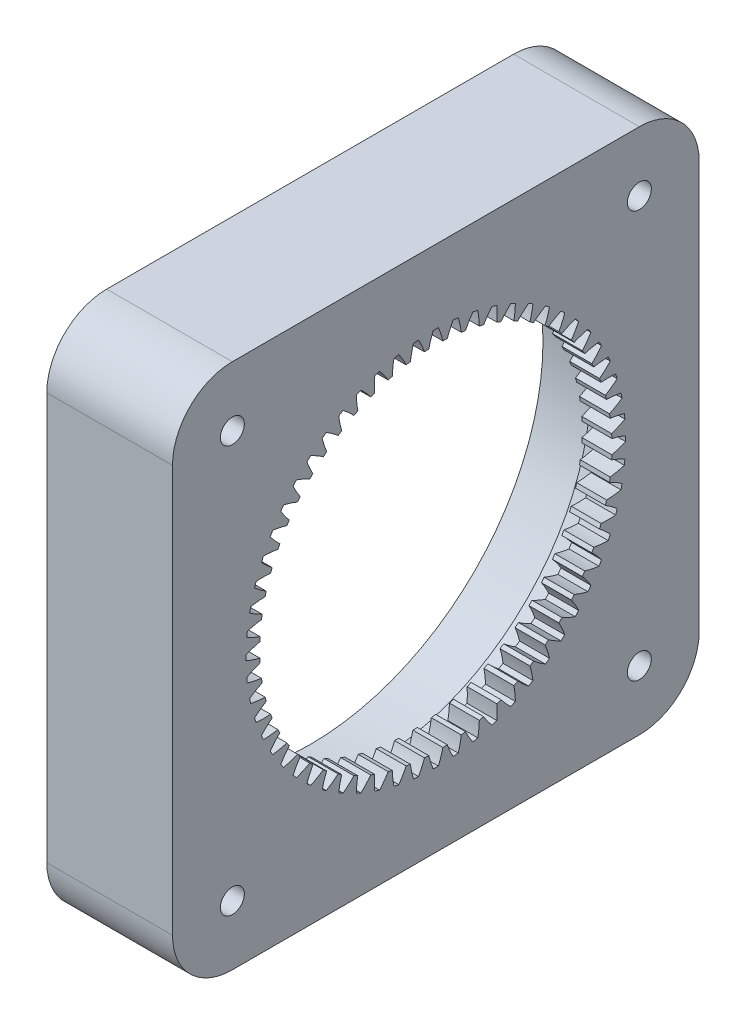
SolidWorks part; units mm, degrees
ref_plane "Plane1" through (0, 0, 0) normal (0, 0, 1) x (1, 0, 0)
ref_plane "Plane2" through (0, 0, 0) normal (0, 1, 0) x (1, 0, 0)
ref_plane "Plane3" through (0, 0, 0) normal (1, 0, 0) x (0, 0, -1)
other "Configuration Table"
sketch "HoldingSke" plane through (0, 0, 0) normal (0, 1, 0) x (1, 0, 0)
  line L0 (0, 0) -> (0.4926, -0.8532)
  line L1 (-15, 0) -> (100, 0) construction
  line L2 (0, 0) -> (-2.1039, 2.3779)
  line L3 (0, 0) -> (-11.863, 4.5341)
  line L4 (0, 0) -> (4.318, 7.479)
  line L5 (0, 0) -> (-23.7986, -8.8762)
  line L6 (0, 0) -> (-10.5278, -7.1032)
  line L7 (-2.1039, 2.3779) -> (3.3635, 27.1825)
  line L8 (-76.2, 3.3929) -> (-54.61, 3.3929)
  line L9 (-67.7845, 28.3722) -> (-49.3413, 33.142)
  line L10 (-76.2, 71.12) -> (104.1128, 71.12)
  line L11 (0, 0) -> (-5, 0)
  line L12 (-76.2, 101.6) -> (-76.162, 101.6)
  line L13 (24.9733, 27.94) -> (52.9518, 28.4284)
  line L14 (24.9733, 27.94) -> (24.9743, 27.94)
  line L15 (24.9733, 27.94) -> (100.4006, 29.5858)
  circle A0 centre (0, 0) radius 44
  circle A1 centre (0, 0) radius 12.7
  circle A2 centre (0, 0) radius 12.7
  dimension "MHD" = 25.4
  dimension "Hub_dia" = 25.4
  dimension "Diameter" = 88
  dimension "Num_teeth" = 60
  dimension "Pitch" = 0.9852
  dimension "Overall_len" = 25.4
  dimension "Show_teeth" = 60
  dimension "Thickness" = 12.7
  dimension "OAL" = 25.4001
  dimension "T_dim" = 21.59
  dimension "Ap" = 14.5
  dimension "H" = 19.05
  dimension "Pitch_radius" = 180.3128
  dimension "Width" = 5
  dimension "Backlash" = 0.038
  dimension "Addendum_fac" = 1
  dimension "Dedendum_fac" = 1.25
  dimension "Clearance_fac" = 0.25
  dimension "Dedendum_add" = 0.001
  dimension "Module" = 1.015
sketch "BasProSke" plane through (0, 0, 0) normal (0, 1, 0) x (1, 0, 0)
  line L0 (-10, 0) -> (60, 0) construction
  line L1 (0, 29.435) -> (0, 44)
  line L2 (0, 29.435) -> (5, 29.435)
  line L3 (5, 29.435) -> (5, 44)
  line L4 (5, 44) -> (0, 44)
  dimension "Diameter" = 88
  dimension "Thickness" = 5
  dimension "Inside_diameter" = 58.87
revolve "Base-Revolve" add sketch "BasProSke" angle 360 about L0
sketch "TooCutSke" plane through (0, 0, 0) normal (1, 0, 0) x (0, 0, -1)
  line L3 (0.8921, 30.4369) -> (0.8921, 53.6633) construction
  line L4 (0, 0) -> (0, 59.563) construction
  line L5 (0, 0) -> (-3.576, 68.2339) construction
  line L6 (-13.6269, 25.8543) -> (36.4024, 28.4763) construction
  circle A0 centre (0, 0) radius 30.45 construction
  circle A1 centre (0, 0) radius 31.7197 construction
  circle A2 centre (0, 0) radius 26.5321 construction
  circle A3 centre (0, 0) radius 29.4096 construction
  arc A4 (1.1829, 29.3858) -> (0.4241, 31.7169) centre (-13.6269, 25.8543) ccw
  arc A5 (1.1829, 29.3858) -> (-1.1829, 29.3858) centre (0, 0) ccw
  arc A6 (0.4241, 31.7169) -> (-0.4241, 31.7169) centre (0, 0) ccw
  arc A7 (-0.4241, 31.7169) -> (-1.1829, 29.3858) centre (13.6269, 25.8543) ccw
  dimension "Pitch_dia" = 60.9
  dimension "Base_dia" = 53.0642
  dimension "Root_dia" = 63.4395
  dimension "Overcut_dia" = 58.8192
  dimension "Flank_rad" = 15.225
  dimension "Half_ang" = 3
  dimension "Half_CT" = 0.8921
extrude "ToothCut" cut sketch "TooCutSke" along normal through all
fillet "Breaks" [suppressed] radius 0.1015
fillet "RootFillets" [suppressed] radius 0.2547
pattern_circular "TeethCuts" count 60 every 6 about axis through (-10, 0, 0) along (1, 0, 0) of "RootFillets", "Breaks", "ToothCut"
sketch "Sketch4" plane through (0, 0, 0) normal (-1, 0, 0) x (0, 0, 1)
  circle A0 centre (0, 0) radius 44
  circle A1 centre (0, 0) radius 38.9
  circle A2 centre (0, 0) radius 44 construction
  dimension "D1" = 77.8
extrude "Boss-Extrude3" add sketch "Sketch4" along normal blind 16
sketch "Sketch7" plane through (5, 0, 0) normal (1, 0, 0) x (0, 0, -1)
  line L0 (0, 44) -> (44, 44)
  line L1 (44, 44) -> (44, 0)
  circle A0 centre (0, 0) radius 44 construction
  arc A1 (44, 0) -> (0, 44) centre (0, 0) ccw
extrude "Boss-Extrude5" add sketch "Sketch7" against normal up to surface (21 mm away) up to face at (-16, 0, 44)
fillet "Fillet1" radius 10 1 edges at (-5.5, 44, -44)
pattern_circular "CirPattern2" count 4 over 360 about axis through (-10, 0, 0) along (-1, 0, 0) of "Boss-Extrude5", "Fillet1"
sketch "Sketch14" plane through (0, 0, 0) normal (-1, 0, 0) x (0, 0, 1)
  circle A0 centre (0, 0) radius 36.9
  circle A1 centre (0, 0) radius 38.9 construction
  circle A2 centre (0, 0) radius 38.9
  dimension "D1" = 2
extrude "Boss-Extrude7" add sketch "Sketch14" along normal blind 6
sketch "Sketch15" plane through (-16, 0, 0) normal (-1, 0, 0) x (0, 0, 1)
  circle A0 centre (-34, 34) radius 2
  circle A1 centre (-34, -34) radius 2
  circle A2 centre (34, -34) radius 2
  circle A3 centre (34, 34) radius 2
  dimension "D1" = 4
extrude "Cut-Extrude1" cut sketch "Sketch15" against normal through all
equation "' \"Module@HoldingSke\" = 6.35"
equation "' \"Num_teeth@HoldingSke\" = 24"
equation "' \"Ap@HoldingSke\" =  14.5"
equation "' \"Ap@HoldingSke\" = 14.5"
equation "' \"Width@HoldingSke\" = 12"
equation "' \"Diameter@HoldingSke\" = 8 * 25.4"
equation "' \"Show_teeth@HoldingSke\" = 100"
equation "' \"Backlash@HoldingSke\" = 0.009 * 25.4"
equation "' \"Addendum_fac@HoldingSke\" = 1.0"
equation "' \"Dedendum_fac@HoldingSke\" = 1.25"
equation "' \"Dedendum_add@HoldingSke\" = 0.00005 * 25.4"
equation "' \"Clearance_fac@HoldingSke\" = 0.25"
equation "\"Pitch@HoldingSke\" = 1 / \"Module@HoldingSke\" "
equation "\"Overcut_dia@TooCutSke\" = (\"Num_teeth@HoldingSke\" - 2 * \"Addendum_fac@HoldingSke\") / \"Pitch@HoldingSke\" - 0.002 * 25.4"
equation "\"Pitch_dia@TooCutSke\" = \"Num_teeth@HoldingSke\" / \"Pitch@HoldingSke\""
equation "\"Base_dia@TooCutSke\" = \"Num_teeth@HoldingSke\" / \"Pitch@HoldingSke\" * cos((\"Ap@HoldingSke\"  * 3.14159265 / 180)) * 0.90"
equation "\"Root_dia@TooCutSke\" = \"Num_teeth@HoldingSke\"  / \"Pitch@HoldingSke\" + 2 *  \"Dedendum_fac@HoldingSke\"/ \"Pitch@HoldingSke\" + \"Dedendum_add@HoldingSke\" * 2"
equation "\"Half_ang@TooCutSke\" = 180 / \"Num_teeth@HoldingSke\""
equation "\"Half_CT@TooCutSke\" = \"Num_teeth@HoldingSke\" / \"Pitch@HoldingSke\" * sin((3.14159265 / 2 / \"Num_teeth@HoldingSke\")) / 2 + 10 * \"Backlash@HoldingSke\" / 4"
equation "\"Flank_rad@TooCutSke\" = \"Num_teeth@HoldingSke\" / \"Pitch@HoldingSke\" / 4"
equation "\"Radius@RootFillets\"= \"Clearance_fac@HoldingSke\" / \"Pitch@HoldingSke\" + \"Dedendum_add@HoldingSke\""
equation "\"Break_rad@Breaks\" = 0.02 / \"Pitch@HoldingSke\" * 5"
equation "\"Num_teeth@TeethCuts\" = int( \"Show_teeth@HoldingSke\" ) + 1"
equation "\"Num_teeth@TeethCuts\" = ((sgn( \"Num_teeth@TeethCuts\" - \"Num_teeth@HoldingSke\" )-1)*( \"Num_teeth@TeethCuts\" - \"Num_teeth@HoldingSke\" ))/-2+ \"Num_teeth@HoldingSke\""
equation "\"Num_teeth@TeethCuts\" = ((sgn( \"Num_teeth@TeethCuts\" - 2.0)+1)*( \"Num_teeth@TeethCuts\" - 2.0))/2 +2.0"
equation "\"Angle@TeethCuts\" = 360.0 / \"Num_teeth@HoldingSke\""
equation "\"Diameter@BasProSke\" = \"Num_teeth@HoldingSke\"  / \"Pitch@HoldingSke\" + 2 *  \"Dedendum_fac@HoldingSke\"/ \"Pitch@HoldingSke\" + \"Dedendum_add@HoldingSke\" * 2 + 0.002 * 25.4"
equation "\"Diameter@BasProSke\" = ((sgn( \"Diameter@BasProSke\"  - \"Diameter@HoldingSke\" )+1)*( \"Diameter@BasProSke\"  - \"Diameter@HoldingSke\" ))/2 + \"Diameter@HoldingSke\""
equation "\"Inside_diameter@BasProSke\" =  (\"Num_teeth@HoldingSke\" - 2 * \"Addendum_fac@HoldingSke\") / \"Pitch@HoldingSke\" "
equation "\"Thickness@BasProSke\"  = \"Width@HoldingSke\""
